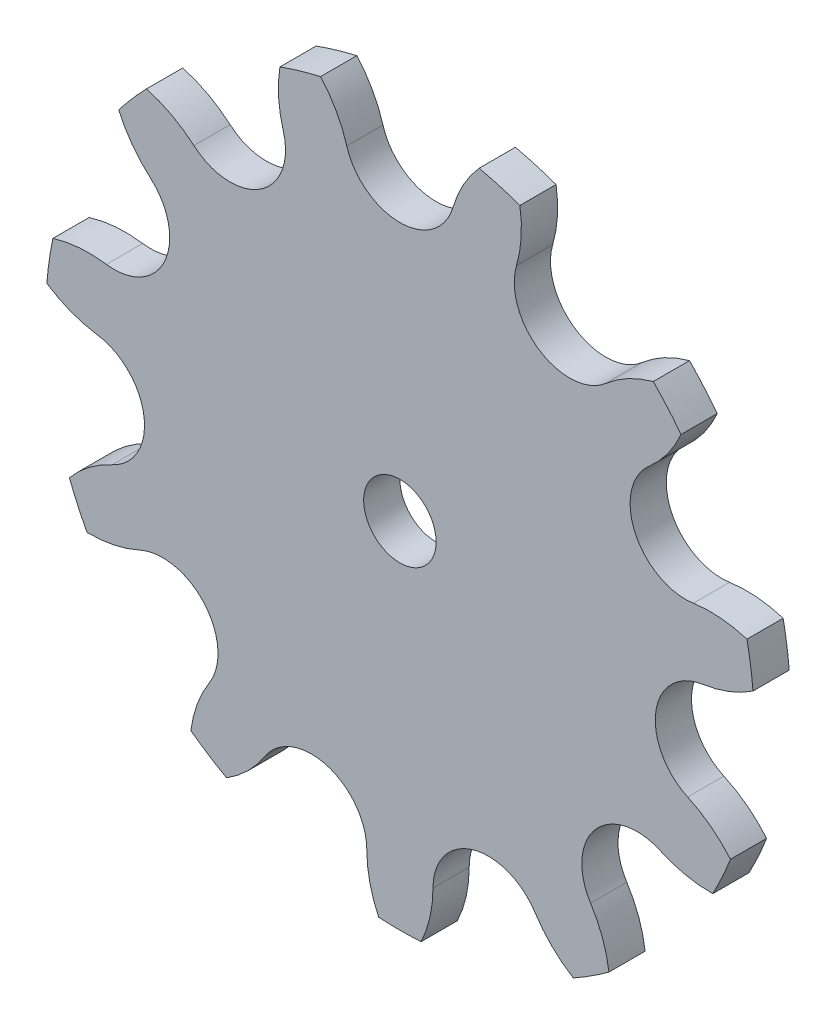
SolidWorks part; units mm, degrees
material "POM Acetal Copolymer"
ref_plane "Alzado" through (0, 0, 0) normal (0, 0, 1) x (1, 0, 0)
ref_plane "Planta" through (0, 0, 0) normal (0, 1, 0) x (1, 0, 0)
ref_plane "Vista lateral" through (0, 0, 0) normal (1, 0, 0) x (0, 0, -1)
sketch "Sk_Disco" plane through (0, 0, 0) normal (0, 0, 1) x (1, 0, 0)
  circle A0 centre (0, 0) radius 25.4361
  circle A1 centre (0, 0) radius 2.6
  dimension "D1" = 50.8722
extrude "Disco" add sketch "Sk_Disco" along normal blind 2.6
sketch "Sk_Hueco" plane through (0, 0, 0) normal (0, 0, 1) x (1, 0, 0)
  line L0 (0, 0) -> (0, 22.5391) construction
  line L1 (0, 0) -> (-12.1856, 18.9611) construction
  line L2 (0, 0) -> (12.1856, 18.9611) construction
  line L3 (0, 22.5391) -> (-12.1856, 18.9611) construction
  line L4 (0, 22.5391) -> (12.1856, 18.9611) construction
  arc A0 (-3.814, 21.4192) -> (3.814, 21.4192) centre (0, 22.5391) ccw
  arc A1 (-3.814, 21.4192) -> (-7.5764, 26.3693) centre (-12.1856, 18.9611) ccw
  arc A2 (7.5764, 26.3693) -> (3.814, 21.4192) centre (12.1856, 18.9611) ccw
  arc A3 (7.5764, 26.3693) -> (-7.5764, 26.3693) centre (0, 0) ccw
  dimension "D6" = 3.975
  dimension "D7" = 27.4361
  dimension "D1" = 22.5391
  dimension "D2" = 22.5391
  dimension "D3" = 22.5391
  dimension "D4" = 32.727
  dimension "D5" = 32.727
extrude "Hueco_diente" cut sketch "Sk_Hueco" along normal through all
ref_axis "Eje_pinon" through (0, 0, -0.13) along (0, 0, 1)
pattern_circular "Matriz_dientes" count 11 over 360 about axis through (0, 0, -0.13) along (0, 0, 1) of "Hueco_diente"
equation "\"Z\"= 11"
equation "\"p\"= 12.7"
equation "\"Dr\"= 7.75"
equation "\"e\"= 2.6"
equation "\"D\"= \"p\" / sin ( 180 / \"Z\" )"
equation "\"De\"= \"p\" * ( 0.6 + 1 / tan ( 180 / \"Z\" ) )"
equation "\"Di\"= \"D\" - \"Dr\""
equation "\"Ang\"= 360 / \"Z\""
equation "\"D1@Sk_Disco\" = \"De\""
equation "\"D1@Disco\" = \"e\""
equation "\"D1@Sk_Hueco\" = \"D\" / 2"
equation "\"D2@Sk_Hueco\" = \"D\" / 2"
equation "\"D3@Sk_Hueco\" = \"D\" / 2"
equation "\"D4@Sk_Hueco\" = \"Ang\""
equation "\"D5@Sk_Hueco\" = \"Ang\""
equation "\"D6@Sk_Hueco\" = \"Dr\" / 2 + 0.1"
equation "\"D7@Sk_Hueco\" = \"De\" / 2 + 2"
equation "\"D1@Matriz_dientes\" = \"Z\""
